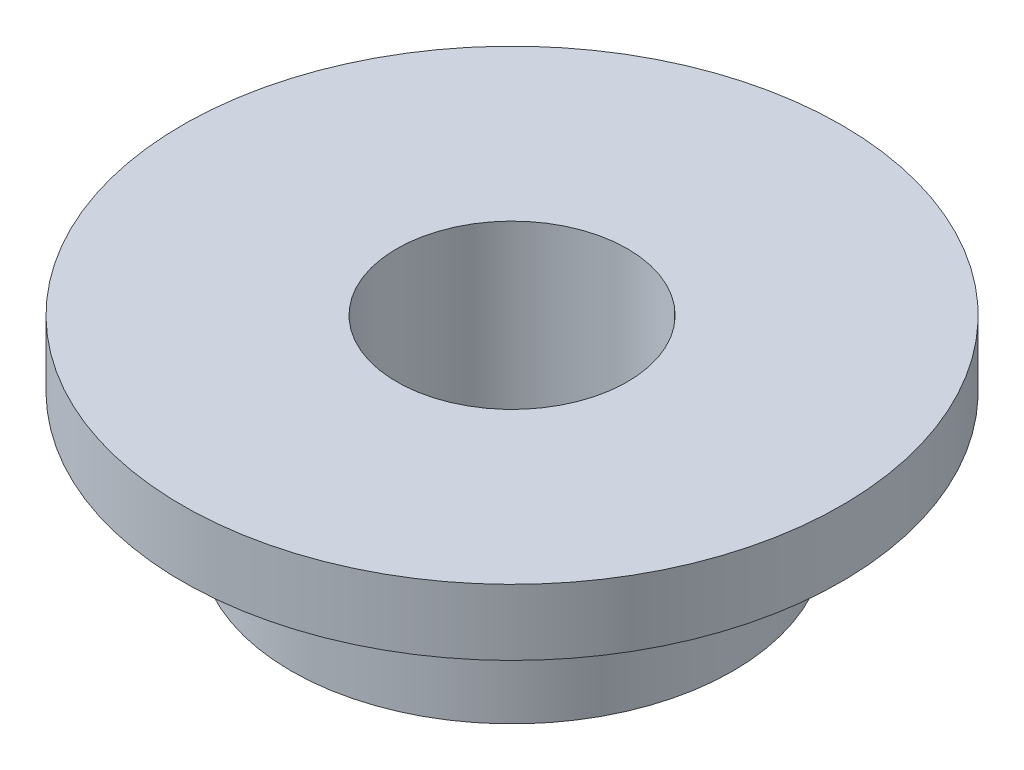
SolidWorks part; units mm, degrees
material "Сталь ШХ15 ГОСТ 801-78"
ref_plane "Plane1" through (0, 0, 0) normal (0, 0, 1) x (1, 0, 0)
ref_plane "Plane2" through (0, 0, 0) normal (0, 1, 0) x (1, 0, 0)
ref_plane "Plane3" through (0, 0, 0) normal (1, 0, 0) x (0, 0, -1)
sketch "Эскиз1" plane through (0, 0, 0) normal (0, 0, 1) x (1, 0, 0)
  line L6 (0, 0) -> (0, 6.4893) construction
  line L7 (3.5, -0.354) -> (3.5, 5.646)
  line L8 (3.5, 5.646) -> (10, 5.646)
  line L9 (10, 5.646) -> (10, 3.646)
  line L10 (10, 3.646) -> (6.7, 3.646)
  line L11 (6.7, 3.646) -> (6.7, -0.354)
  line L12 (6.7, -0.354) -> (3.5, -0.354)
  dimension "D1" = 3.5
  dimension "D2" = 6.7
  dimension "D3" = 10
  dimension "D4" = 2
  dimension "D5" = 6
revolve "Повернуть1" add sketch "Эскиз1" angle 360 about L6
